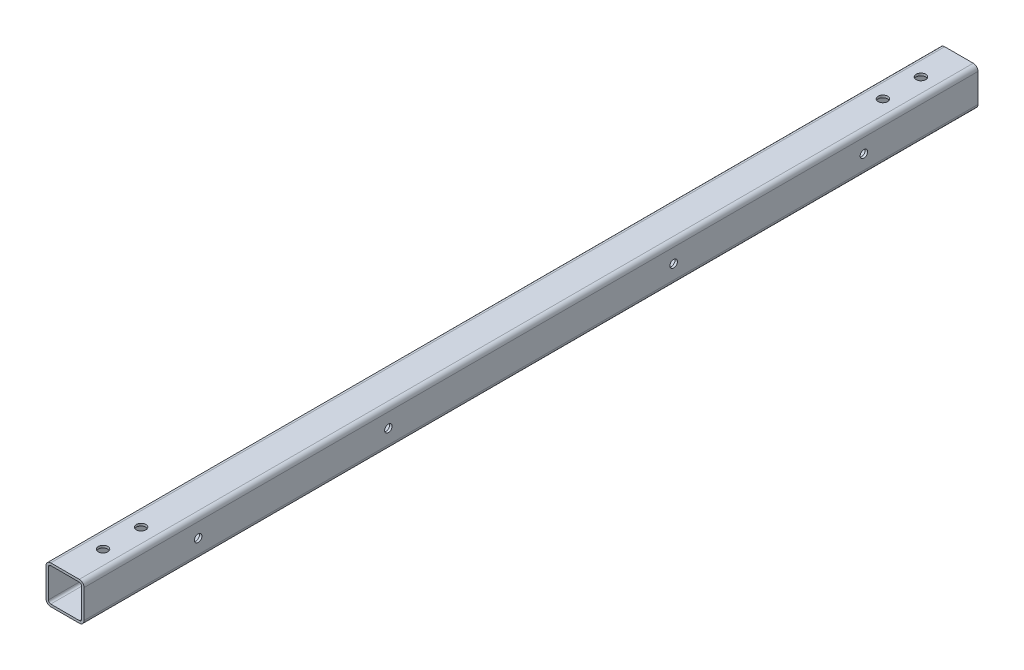
SolidWorks part; units mm, degrees
material "3003 Alloy"
ref_plane "Front" through (0, 0, 0) normal (0, 0, 1) x (1, 0, 0)
ref_plane "Top" through (0, 0, 0) normal (0, 1, 0) x (1, 0, 0)
ref_plane "Right" through (0, 0, 0) normal (1, 0, 0) x (0, 0, -1)
sketch "Sketch1" plane through (0, 0, 0) normal (0, 0, 1) x (1, 0, 0)
  line L0 (-12.7, 12.7) -> (12.7, 12.7)
  line L1 (-12.7, 12.7) -> (-12.7, -12.7)
  line L2 (12.7, -12.7) -> (-12.7, -12.7)
  line L3 (12.7, -12.7) -> (12.7, 12.7)
  line L4 (-12.7, -12.7) -> (12.7, 12.7) construction
  dimension "square" = 25.4
extrude "Base-Extrude" add sketch "Sketch1" along normal mid plane 596.9
fillet "Fillet1" radius 3.175 4 edges at (-12.7, 12.7, 0) (-12.7, -12.7, 0) (12.7, 12.7, 0) (12.7, -12.7, 0)
shell "Shell1" thickness 1.5875 removed face at (0, 0, -298.45) removed face at (0, 0, 298.45)
sketch "Sketch3" plane through (-12.7, 0, 0) normal (-1, 0, 0) x (0, 0, 1)
  line L0 (-298.45, 0) -> (-158.75, 0) construction
  line L1 (-298.45, 9.525) -> (-298.45, -9.525) construction
  circle A0 centre (-209.55, 0) radius 3.175
  circle A2 centre (-158.75, 0) radius 3.175
  dimension "D2" = 6.35
  dimension "D1" = 139.7
  dimension "D3" = 88.9
extrude "tank" [suppressed] cut sketch "Sketch3" against normal up to next
sketch "Sketch4" plane through (0, -12.7, 0) normal (0, -1, 0) x (1, 0, 0)
  line L4 (0, 298.45) -> (0, -298.45) construction
  line L7 (9.525, 298.45) -> (-9.525, 298.45) construction
  line L8 (9.525, -298.45) -> (-9.525, -298.45) construction
  circle A4 centre (0, 273.05) radius 3.175
  circle A5 centre (0, 247.65) radius 3.175
  circle A6 centre (0, -247.65) radius 3.175
  circle A7 centre (0, -273.05) radius 3.175
  dimension "D5" = 6.35
  dimension "D1" = 25.4
  dimension "D2" = 50.8
  dimension "D3" = 25.4
  dimension "D4" = 50.8
extrude "Cut-Extrude1" cut sketch "Sketch4" against normal through all
sketch "Sketch5" plane through (0, -12.7, 0) normal (0, -1, 0) x (1, 0, 0)
  line L0 (0, -298.45) -> (0, 298.45) construction
  line L1 (9.525, -298.45) -> (-9.525, -298.45) construction
  line L2 (9.525, 298.45) -> (-9.525, 298.45) construction
  circle A2 centre (0, 273.05) radius 3.175
  circle A3 centre (0, 247.65) radius 3.175
  circle A6 centre (0, -273.05) radius 3.175
  circle A7 centre (0, -247.65) radius 3.175
  dimension "D3" = 6.35
  dimension "D1" = 25.4
  dimension "D2" = 50.8
  dimension "D4" = 50.8
  dimension "D5" = 25.4
extrude "Cut-Extrude2" [suppressed] cut sketch "Sketch5" against normal through all
sketch "Sketch6" plane through (11.1125, 0, 0) normal (-1, 0, 0) x (0, 0, 1)
  line L0 (-298.45, 9.525) -> (-298.45, -9.525) construction
  line L1 (298.45, 9.525) -> (298.45, -9.525) construction
  line L2 (298.45, -12.7) -> (-298.45, -12.7) construction
  circle A2 centre (-95.25, 0) radius 2.5
  circle A3 centre (-222.25, 0) radius 2.5
  circle A6 centre (222.25, 0) radius 2.5
  circle A7 centre (95.25, 0) radius 2.5
  dimension "D1" = 76.2
  dimension "D2" = 127
  dimension "D3" = 127
  dimension "D4" = 76.2
  dimension "D5" = 12.7
extrude "Cut-Extrude3" cut sketch "Sketch6" against normal up to next
